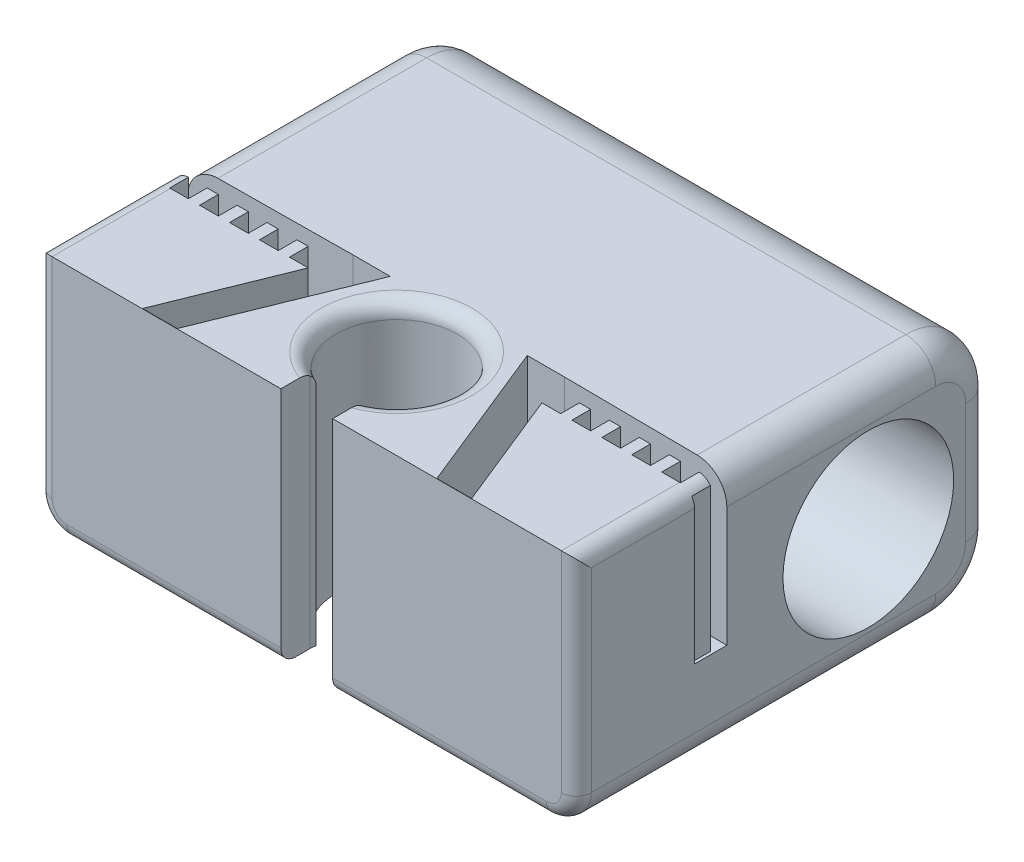
SolidWorks part; units mm, degrees
ref_plane "Alzado" through (0, 0, 0) normal (0, 0, 1) x (1, 0, 0)
ref_plane "Planta" through (0, 0, 0) normal (0, 1, 0) x (1, 0, 0)
ref_plane "Vista lateral" through (0, 0, 0) normal (1, 0, 0) x (0, 0, -1)
sketch "Croquis1" plane through (0, 0, 0) normal (0, 1, 0) x (1, 0, 0)
  line L0 (-16.125, -12.8625) -> (37.0847, -12.8625) construction
  line L1 (-16.125, 9.1375) -> (19.875, 9.1375)
  line L2 (-16.125, 9.1375) -> (-16.125, -18.8625)
  line L3 (-16.125, -18.8625) -> (0.1467, -18.8625)
  line L4 (19.875, 9.1375) -> (19.875, -18.8625)
  line L5 (19.875, 9.1375) -> (-16.125, -18.8625) construction
  line L6 (1.875, -16.9125) -> (1.875, -18.8125) construction
  line L7 (3.6033, -16.9125) -> (3.6033, -18.8625)
  line L8 (0.1467, -16.9125) -> (0.1467, -18.8625)
  line L9 (3.6033, -18.8625) -> (19.875, -18.8625)
  line L10 (-16.1265, 0.6375) -> (22.0746, 0.6375) construction
  line L11 (1.875, -12.8625) -> (1.875, 9.1375) construction
  arc A0 (3.5635, -16.5437) -> (0.1865, -16.5437) centre (1.875, -12.8625) ccw
  arc A1 (3.6033, -16.9125) -> (3.5635, -16.5437) centre (1.875, -16.9125) ccw
  arc A3 (0.1865, -16.5437) -> (0.1467, -16.9125) centre (1.875, -16.9125) ccw
  point P10 (1.875, -17.8625)
  dimension "D4" = 3.4566
  dimension "D7" = 4.05
  dimension "D1" = 18
  dimension "D2" = 28
  dimension "D3" = 6
  dimension "D5" = 13.5
  dimension "D6" = 18
extrude "Saliente-Extruir1" add sketch "Croquis1" along normal blind 16
sketch "Croquis5" plane through (19.875, 0, 0) normal (1, 0, 0) x (0, 0, -1)
  line L0 (-12.8625, 19.8022) -> (-12.8625, -6.4895) construction
  line L1 (-18.8625, 16) -> (-18.8625, 0) construction
  line L2 (0.6375, 20.6011) -> (0.6375, -8.3415) construction
  line L3 (-18.8625, 8) -> (9.5862, 8) construction
  circle A0 centre (0.6375, 8) radius 5.7
  dimension "D3" = 11.4
  dimension "D1" = 6
  dimension "D2" = 13.5
extrude "Cortar-Extruir1" cut sketch "Croquis5" against normal blind 38
sketch "Croquis8" plane through (0, 0, 0) normal (0, -1, 0) x (1, 0, 0)
  line L2 (-2.175, 12.8625) -> (5.925, 12.8625)
  arc A0 (0.1865, 16.5437) -> (3.5635, 16.5437) centre (1.875, 12.8625) ccw construction
  arc A1 (-2.175, 12.8625) -> (5.925, 12.8625) centre (1.875, 12.8625) ccw
extrude "Saliente-Extruir2" add sketch "Croquis8" against normal blind 0.6
sketch "Croquis9" plane through (0, 16, 0) normal (0, 1, 0) x (1, 0, 0)
  line L0 (1.875, -12.8625) -> (1.875, 4.8397) construction
  line L1 (5.925, -12.8625) -> (-2.175, -12.8625) construction
  line L2 (-2.175, -12.8625) -> (-2.175, 5.5668) construction
  line L3 (-15.9292, -9.7125) -> (-15.9292, -10.9625)
  line L4 (-15.1792, -9.7125) -> (-15.9292, -9.7125)
  line L5 (-15.1792, -10.9625) -> (-15.1792, -9.7125)
  line L6 (-13.9292, -10.9625) -> (-15.1792, -10.9625)
  line L7 (-13.9292, -9.7125) -> (-13.9292, -10.9625)
  line L8 (-13.1792, -9.7125) -> (-13.9292, -9.7125)
  line L9 (-13.1792, -10.9625) -> (-13.1792, -9.7125)
  line L10 (-11.9292, -10.9625) -> (-13.1792, -10.9625)
  line L11 (-11.9292, -9.7125) -> (-11.9292, -10.9625)
  line L12 (-11.1792, -9.7125) -> (-11.9292, -9.7125)
  line L13 (-11.1792, -10.9625) -> (-11.1792, -9.7125)
  line L14 (-9.9292, -10.9625) -> (-11.1792, -10.9625)
  line L15 (-9.9292, -9.7125) -> (-9.9292, -10.9625)
  line L16 (-9.9292, -9.7125) -> (-9.1792, -9.7125)
  line L17 (-9.1792, -9.7125) -> (-9.1792, -10.9625)
  line L18 (-7.9292, -10.9625) -> (-9.1792, -10.9625)
  line L19 (-7.9292, -10.9625) -> (-7.9292, -9.7125)
  line L20 (-7.9292, -9.7125) -> (-7.1792, -9.7125)
  line L21 (1.875, -8.8125) -> (-16.125, -8.8125) construction
  line L22 (-7.1792, -9.7125) -> (-7.1792, -10.9625)
  line L23 (-5.9292, -10.9625) -> (-7.1792, -10.9625)
  line L24 (-5.9292, -10.9625) -> (-9.1129, -18.8425)
  line L25 (-2.7007, -8.7125) -> (-6.7935, -18.8425)
  line L26 (-5.1792, -8.7125) -> (-2.7007, -8.7125)
  line L27 (-5.1792, -8.7125) -> (-16.125, -8.8125)
  line L28 (-16.125, 9.1375) -> (-16.125, -18.8625) construction
  line L29 (-16.125, -8.8125) -> (-16.125, -10.9625)
  line L30 (-15.9292, -10.9625) -> (-16.125, -10.9625)
  line L31 (-9.1129, -18.8425) -> (-6.7935, -18.8425)
  line L32 (12.8629, -18.8425) -> (10.5435, -18.8425)
  line L33 (19.6792, -10.9625) -> (19.875, -10.9625)
  line L34 (19.875, -8.8125) -> (19.875, -10.9625)
  line L35 (8.9292, -8.7125) -> (19.875, -8.8125)
  line L36 (8.9292, -8.7125) -> (6.4507, -8.7125)
  line L37 (6.4507, -8.7125) -> (10.5435, -18.8425)
  line L38 (9.6792, -10.9625) -> (12.8629, -18.8425)
  line L39 (9.6792, -10.9625) -> (10.9292, -10.9625)
  line L40 (10.9292, -9.7125) -> (10.9292, -10.9625)
  line L41 (11.6792, -9.7125) -> (10.9292, -9.7125)
  line L42 (11.6792, -10.9625) -> (11.6792, -9.7125)
  line L43 (11.6792, -10.9625) -> (12.9292, -10.9625)
  line L44 (12.9292, -9.7125) -> (12.9292, -10.9625)
  line L45 (13.6792, -9.7125) -> (12.9292, -9.7125)
  line L46 (13.6792, -9.7125) -> (13.6792, -10.9625)
  line L47 (13.6792, -10.9625) -> (14.9292, -10.9625)
  line L48 (14.9292, -10.9625) -> (14.9292, -9.7125)
  line L49 (14.9292, -9.7125) -> (15.6792, -9.7125)
  line L50 (15.6792, -9.7125) -> (15.6792, -10.9625)
  line L51 (15.6792, -10.9625) -> (16.9292, -10.9625)
  line L52 (16.9292, -10.9625) -> (16.9292, -9.7125)
  line L53 (16.9292, -9.7125) -> (17.6792, -9.7125)
  line L54 (17.6792, -9.7125) -> (17.6792, -10.9625)
  line L55 (17.6792, -10.9625) -> (18.9292, -10.9625)
  line L56 (18.9292, -10.9625) -> (18.9292, -9.7125)
  line L57 (18.9292, -9.7125) -> (19.6792, -9.7125)
  line L58 (19.6792, -9.7125) -> (19.6792, -10.9625)
  arc A0 (3.5635, -16.5437) -> (0.1865, -16.5437) centre (1.875, -12.8625) ccw construction
  arc A1 (5.925, -12.8625) -> (-2.175, -12.8625) centre (1.875, -12.8625) ccw construction
extrude "Cortar-Extruir2" cut sketch "Croquis9" against normal blind 10
fillet "Redondeo1" radius 4 2 edges at (1.875, 16, -9.1375) (1.875, 0, -9.1375)
fillet "Redondeo2" radius 2 10 edges at (-16.125, 16, 1.8375) (-16.125, 14.8284, -7.9659) (-16.125, 8, -9.1375) (-16.125, 1.1716, -7.9659) (19.875, 0, 6.8625) (19.875, 16, 1.8375) (-16.125, 0, 6.8625) (19.875, 1.1716, -7.9659) (19.875, 8, -9.1375) (19.875, 14.8284, -7.9659)
fillet "Redondeo3" radius 1 1 edges at (1.875, 16, 8.8125)
fillet "Redondeo5" radius 1 8 edges at (10.7391, 0, 18.8625) (19.2892, 0.5858, 18.8625) (-6.9891, 0, 18.8625) (-15.5392, 0.5858, 18.8625) (19.875, 9, 18.8625) (-16.125, 9, 18.8625) (-16.125, 16, 14.9125) (19.875, 16, 14.9125)
sketch "Croquis10" plane through (-16.125, 0, 0) normal (-1, 0, 0) x (0, 0, 1)
  circle A0 centre (-0.6375, 8) radius 5.7 construction
  circle A1 centre (-0.6375, 8) radius 5.7
  circle A2 centre (-0.6375, 8) radius 4.7
extrude "Saliente-Extruir3" add sketch "Croquis10" against normal blind 2
